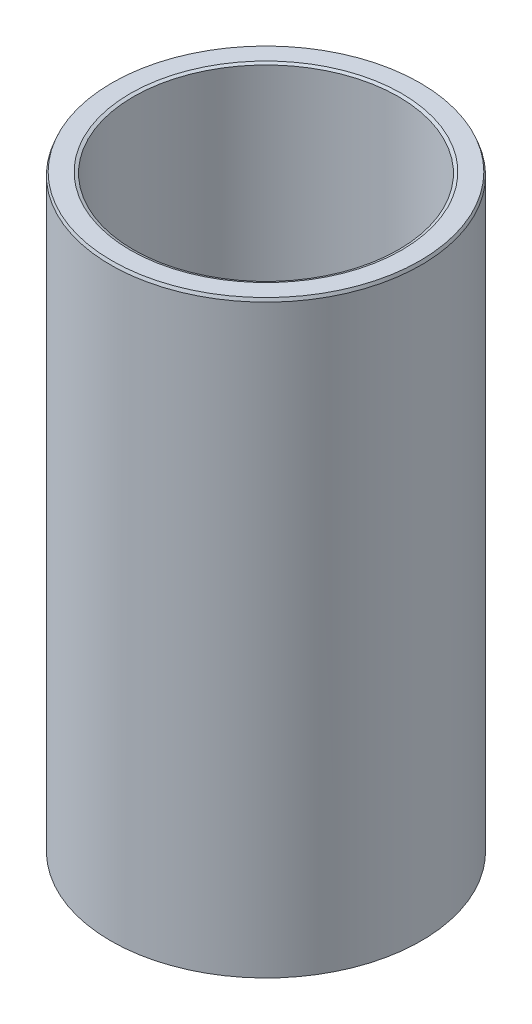
SolidWorks part; units mm, degrees
ref_plane "Front Plane" through (0, 0, 0) normal (0, 0, 1) x (1, 0, 0)
ref_plane "Top Plane" through (0, 0, 0) normal (0, 1, 0) x (1, 0, 0)
ref_plane "Right Plane" through (0, 0, 0) normal (1, 0, 0) x (0, 0, -1)
sketch "Sketch1" plane through (0, 0, 0) normal (0, 1, 0) x (1, 0, 0)
  circle A0 centre (0, 0) radius 35
  dimension "SLEEVE_OD" = 70
extrude "Boss-Extrude1" add sketch "Sketch1" along normal blind 132.906
sketch "Sketch2" plane through (0, 0, 0) normal (0, 1, 0) x (1, 0, 0)
  circle A0 centre (0, 0) radius 29.8823
  dimension "BORE_D" = 59.7647
extrude "Cut-Extrude1" cut sketch "Sketch2" along normal through all
chamfer "Chamfer1" distance 0.7026 angle 21.333 4 edges at (0, 132.906, 29.8823) (0, 0, 29.8823) (0, 0, 35) (0, 132.906, 35) first distance on face at (0, 132.906, 29.8823) first distance on face at (0, 0, 29.8823) first distance on face at (0, 132.906, 35)
